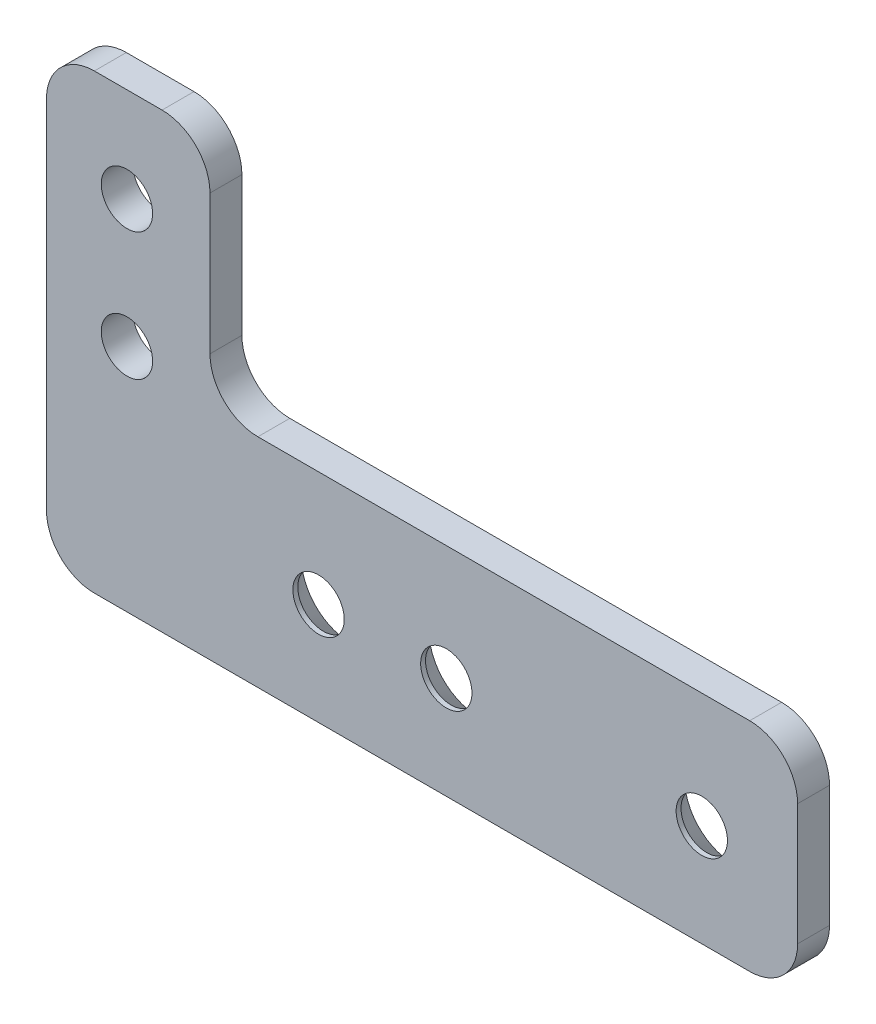
SolidWorks part; units mm, degrees
material "6061-T6 (SS)"
ref_plane "Front Plane" through (0, 0, 0) normal (0, 0, 1) x (1, 0, 0)
ref_plane "Top Plane" through (0, 0, 0) normal (0, 1, 0) x (1, 0, 0)
ref_plane "Right Plane" through (0, 0, 0) normal (1, 0, 0) x (0, 0, -1)
sketch "Sketch1" plane through (0, 0, 0) normal (0, 0, 1) x (1, 0, 0)
  line L0 (41.275, -11.049) -> (-33.401, -11.049) construction
  line L1 (-41.275, -23.749) -> (41.275, -23.749)
  line L2 (-41.275, -23.749) -> (-41.275, 23.749)
  line L3 (-41.275, 23.749) -> (41.275, 23.749)
  line L4 (41.275, -23.749) -> (41.275, 23.749)
  line L5 (-41.275, -23.749) -> (41.275, 23.749) construction
  line L6 (-41.275, 23.749) -> (41.275, -23.749) construction
  line L7 (41.275, 23.749) -> (-17.145, 23.749)
  line L8 (41.275, 23.749) -> (41.275, 0.381)
  line L9 (41.275, 0.381) -> (-17.145, 0.381)
  line L10 (-17.145, 23.749) -> (-17.145, 0.381)
  line L11 (-41.275, -23.749) -> (-33.401, -23.749)
  line L12 (-41.275, -23.749) -> (-41.275, 23.749)
  line L13 (-41.275, 23.749) -> (-33.401, 23.749)
  line L14 (-33.401, -23.749) -> (-33.401, 23.749)
  line L15 (-33.401, -23.749) -> (41.275, -23.749)
  line L16 (-33.401, -23.749) -> (-33.401, -21.209)
  line L17 (-33.401, -21.209) -> (41.275, -21.209)
  line L18 (41.275, -23.749) -> (41.275, -21.209)
  line L19 (-33.401, 23.876) -> (-17.145, 23.876) construction
  circle A0 centre (-25.4, -11.049) radius 2.5527
  circle A1 centre (-25.4, 1.651) radius 2.5527
  circle A2 centre (-25.4, 14.351) radius 2.5527
  point P0 (0, 0)
  point P22 (31.75, -11.049)
  point P23 (-6.35, -11.049)
  point P24 (6.35, -11.049)
  dimension "D7" = 5.1054
  dimension "D1" = 82.55
  dimension "D2" = 47.498
  dimension "D3" = 24.13
  dimension "D4" = 24.13
  dimension "D5" = 7.874
  dimension "D6" = 47.498
  dimension "D8" = 19.05
  dimension "D9" = 12.7
  dimension "D10" = 12.7
  dimension "D11" = 12.7
  dimension "D12" = 9.525
  dimension "D13" = 25.4
  dimension "D14" = 12.7
  dimension "D15" = 8.001
  dimension "D16" = 2.54
extrude "Boss-Extrude1" add sketch "Sketch1" along normal blind 3.175 contours L14 L17 L4 L9 L10 L3 A2 A1 A0 | A0 region at (-0.8769, -6.375, 0) region at (-25.4, -11.049, 0)
fillet "Fillet1" radius 4.7625 6 edges at (-33.401, 23.749, 1.5875) (-17.145, 23.749, 1.5875) (-17.145, 0.381, 1.5875) (41.275, 0.381, 1.5875) (41.275, -21.209, 1.5875) (-33.401, -21.209, 1.5875)
hole_wizard "CSK for #10 Flat Head Machine Screw3" positions "Sketch6" profile "Sketch7" countersink size "#10" standard "ANSI Inch" end condition through all
sketch "Sketch6" plane through (0, 0, 0) normal (0, 0, -1) x (-1, 0, 0)
  point P0 (-31.75, -11.049)
  point P3 (-6.35, -11.049)
  point P6 (6.35, -11.049)
sketch "Sketch7" plane through (31.75, -11.049, 0) normal (1, 0, 0) x (0, 1, 0)
  line L0 (0, 0) -> (0, 3.175)
  line L1 (0, 3.175) -> (2.5527, 3.175)
  line L2 (2.5527, 3.175) -> (2.5527, 2.6882)
  line L3 (2.5527, 2.6882) -> (4.8895, 0)
  line L5 (4.8895, 0) -> (0, 0)
  line L6 (-2.5527, 2.6882) -> (-4.8895, 0) construction
  line L11 (0, -6.35) -> (0, 107.95) construction
  dimension "Thru Hole Dia." = 5.1054
  dimension "Thru Hole Depth" = 3.175
  dimension "Near C'Sink Dia." = 9.779
  dimension "Near C'Sink Angle" = 82
